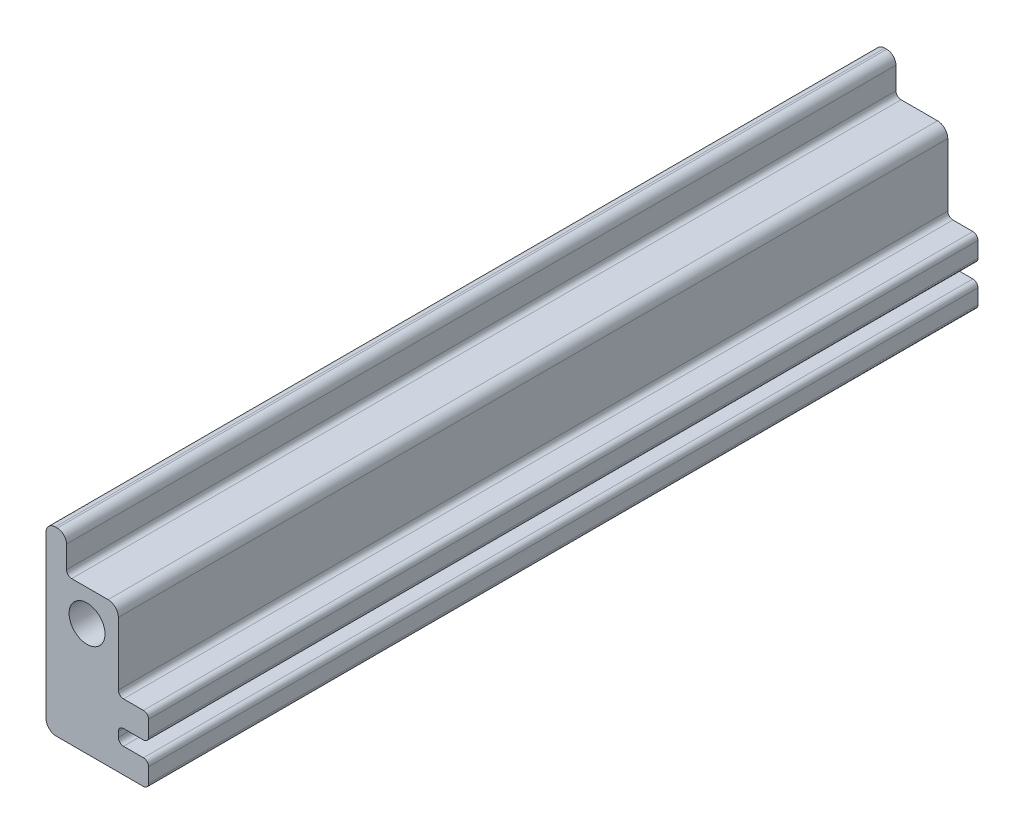
SolidWorks part; units mm, degrees
material "Pink Foam"
ref_plane "Front Plane" through (0, 0, 0) normal (0, 0, 1) x (1, 0, 0)
ref_plane "Top Plane" through (0, 0, 0) normal (0, 1, 0) x (1, 0, 0)
ref_plane "Right Plane" through (0, 0, 0) normal (1, 0, 0) x (0, 0, -1)
sketch "Sketch1" plane through (0, 0, 0) normal (0, 0, 1) x (1, 0, 0)
  line L1 (34.925, -69.85) -> (-19.05, -69.85)
  line L2 (38.1, -41.7472) -> (38.1, -32.2222)
  line L3 (34.925, -29.0472) -> (22.5628, -29.0472)
  line L4 (-25.4, -63.5) -> (-25.4, 36.2978)
  line L6 (19.3878, -25.8722) -> (19.3878, 13.0378)
  line L7 (13.0378, 19.3878) -> (-9.525, 19.3878)
  line L8 (-12.7, 22.5628) -> (-12.7, 36.2978)
  line L9 (-18.415, 42.0128) -> (-19.685, 42.0128)
  line L11 (34.925, -44.9222) -> (22.5628, -44.9222)
  line L12 (11.1125, 0) -> (19.3878, 0) construction
  line L14 (0, 11.1125) -> (0, 19.3878) construction
  line L15 (19.3878, -48.0972) -> (19.3878, -51.2722)
  line L19 (22.5628, -54.4472) -> (34.925, -54.4472)
  line L20 (38.1, -66.675) -> (38.1, -57.6222)
  circle A0 centre (0, 0) radius 11.1125
  arc A3 (-9.525, 19.3878) -> (-12.7, 22.5628) centre (-9.525, 22.5628) cw
  arc A4 (-19.05, -69.85) -> (-25.4, -63.5) centre (-19.05, -63.5) cw
  arc A6 (38.1, -32.2222) -> (34.925, -29.0472) centre (34.925, -32.2222) ccw
  arc A8 (19.3878, 13.0378) -> (13.0378, 19.3878) centre (13.0378, 13.0378) ccw
  arc A9 (-12.7, 36.2978) -> (-18.415, 42.0128) centre (-18.415, 36.2978) ccw
  arc A10 (-19.685, 42.0128) -> (-25.4, 36.2978) centre (-19.685, 36.2978) ccw
  arc A11 (19.3878, -25.8722) -> (22.5628, -29.0472) centre (22.5628, -25.8722) ccw
  arc A12 (22.5628, -44.9222) -> (19.3878, -48.0972) centre (22.5628, -48.0972) ccw
  arc A13 (34.925, -44.9222) -> (38.1, -41.7472) centre (34.925, -41.7472) ccw
  arc A14 (22.5628, -54.4472) -> (19.3878, -51.2722) centre (22.5628, -51.2722) cw
  arc A15 (34.925, -69.85) -> (38.1, -66.675) centre (34.925, -66.675) ccw
  arc A16 (34.925, -54.4472) -> (38.1, -57.6222) centre (34.925, -57.6222) cw
  point P9 (0, -11.1125)
  point P15 (0, 11.1125)
  point P16 (11.1125, 0)
  point P31 (-12.7, 19.3878)
  point P34 (-25.4, -69.85)
  point P40 (38.1, -29.0472)
  point P47 (-12.7, 42.0128)
  point P50 (-25.4, 42.0128)
  point P56 (19.3878, -54.4472)
  point P59 (38.1, -69.85)
  point P62 (38.1, -54.4472)
  dimension "D1" = 22.225
  dimension "D6" = 8.2753
  dimension "D10" = 3.175
  dimension "D11" = 6.35
  dimension "D12" = 5.715
  dimension "D5" = 3.175
  dimension "D7" = 6.35
  dimension "D13" = 29.0472
  dimension "D14" = 3.175
  dimension "D15" = 18.7122
  dimension "D16" = 3.175
  dimension "D17" = 3.175
  dimension "D18" = 15.875
  dimension "D20" = 3.175
  dimension "D21" = 3.175
  dimension "D22" = 3.175
  dimension "D3" = 69.85
  dimension "D4" = 25.4
  dimension "D8" = 22.625
  dimension "D9" = 12.7
  dimension "D19" = 19.3878
  dimension "D23" = 9.525
extrude "Boss-Extrude1" add sketch "Sketch1" along normal blind 513.461
